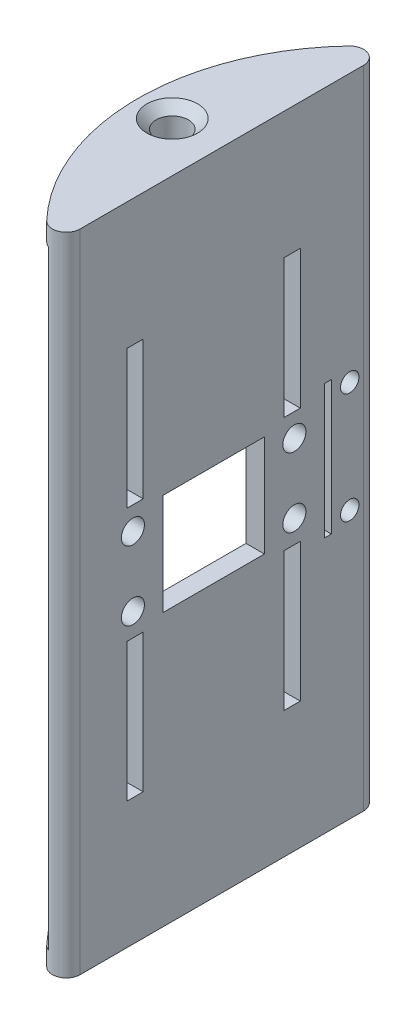
SolidWorks part; units mm, degrees
ref_plane "Front Plane" through (0, 0, 0) normal (1, 0, 0) x (0, 1, 0)
ref_plane "Top Plane" through (0, 0, 0) normal (0, 0, 1) x (0, 1, 0)
ref_plane "Right Plane" through (0, 0, 0) normal (0, 1, 0) x (-1, 0, 0)
sketch "Sketch1" plane through (0, 0, 0) normal (0, 0, 1) x (0, 1, 0)
  line L0 (-8.186, 0) -> (-8.186, -21.2483)
  line L1 (-8.186, -21.2483) -> (131.814, -21.2483)
  line L2 (131.814, -21.2483) -> (131.814, 0)
  line L3 (131.814, 0) -> (123.814, 0)
  line L4 (123.814, 0) -> (123.814, -17.2483)
  line L5 (123.814, -17.2483) -> (-0.186, -17.2483)
  line L6 (-0.186, -17.2483) -> (-0.186, 0)
  line L7 (-0.186, 0) -> (-8.186, 0)
  line L8 (-12.186, -30.6238) -> (-12.186, -16.002) construction
  line L10 (135.814, -16.002) -> (135.814, 53.9758) construction
  dimension "D1" = 4
  dimension "D2" = 8
  dimension "D3" = 4
  dimension "D4" = 4
  dimension "D5" = 140
extrude "Boss-Extrude1" add sketch "Sketch1" along normal blind 75
sketch "Sketch2" plane through (0, -8.186, 0) normal (0, -1, 0) x (1, 0, 0)
  line L0 (21.2483, 37.5) -> (0, 37.5) construction
  line L1 (21.2483, 75) -> (21.2483, 0) construction
  line L2 (0, 75) -> (0, 0) construction
  circle A0 centre (10.5, 37.5) radius 3.5
  dimension "D1" = 7
  dimension "D2" = 7
extrude "Cut-Extrude1" cut sketch "Sketch2" against normal offset from surface (7 mm away) 1 up to face at (8.6242, -0.186, 37.5)
sketch "Sketch3" plane through (0, 131.814, 0) normal (0, 1, 0) x (-1, 0, 0)
  circle A0 centre (-10.5, 37.5) radius 3.5 construction
  circle A1 centre (-10.5, 37.5) radius 3.5
extrude "Cut-Extrude2" cut sketch "Sketch3" against normal offset from surface (7 mm away) 1 up to face at (8.6242, 123.814, 37.5)
sketch "Sketch6" plane through (0, -0.186, 0) normal (0, 1, 0) x (-1, 0, 0)
  line L4 (-17.2483, 0) -> (0, 0)
  line L5 (0, 0) -> (0, 75)
  line L6 (0, 75) -> (-17.2483, 75)
  line L7 (-17.2483, 75) -> (-17.2483, 0)
  line L8 (-17.2483, 0) -> (0, 0)
  line L9 (0, 0) -> (0, 75)
  line L10 (0, 75) -> (-17.2483, 75)
  line L11 (-17.2483, 75) -> (-17.2483, 0)
  circle A1 centre (-10.5, 37.5) radius 4
  circle A3 centre (-10.5, 37.5) radius 3.5 construction
  dimension "D2" = 8
  dimension "D1" = 0
extrude "Cut-Extrude3" cut sketch "Sketch6" against normal blind 4
sketch "Sketch7" plane through (0, 123.814, 0) normal (0, -1, 0) x (1, 0, 0)
  line L4 (0, 0) -> (17.2483, 0)
  line L5 (17.2483, 0) -> (17.2483, 75)
  line L6 (17.2483, 75) -> (0, 75)
  line L7 (0, 75) -> (0, 0)
  line L8 (0, 0) -> (17.2483, 0)
  line L9 (17.2483, 0) -> (17.2483, 75)
  line L10 (17.2483, 75) -> (0, 75)
  line L11 (0, 75) -> (0, 0)
  circle A2 centre (10.5, 37.5) radius 4
  circle A3 centre (10.5, 37.5) radius 3.5 construction
  dimension "D1" = 8
  dimension "D2" = 0
extrude "Cut-Extrude4" cut sketch "Sketch7" against normal blind 4
fillet "Fillet6" radius 4 2 edges at (10.5, 127.814, 33.5) (10.5, -4.186, 41.5)
chamfer "Chamfer1" distance 2 angle 45 2 edges at (10.5, -8.186, 34) (10.5, 131.814, 41)
sketch "Sketch10" plane through (0, -8.186, 0) normal (0, -1, 0) x (1, 0, 0)
  line L6 (21.2483, 75) -> (0, 75)
  line L7 (0, 75) -> (0, 0) construction
  line L8 (0, 75) -> (21.2483, 75) construction
  line L9 (0, 75) -> (0, 0)
  line L10 (0, 0) -> (21.2483, 0)
  arc A1 (21.2483, 75) -> (21.2483, 0) centre (50.6551, 37.5) ccw
  circle A4 centre (10.5, 37.5) radius 5.5 construction
  dimension "D1" = 2
extrude "Cut-Extrude9" cut sketch "Sketch10" against normal through all
fillet "Fillet11" radius 3 2 edges at (21.2483, 61.814, 75) (21.2483, 61.814, 0)
sketch "Sketch14" plane through (21.2483, 0, 0) normal (1, 0, 0) x (0, 1, 0)
  line L2 (131.814, 5.8571) -> (131.814, 74.4281) construction
  line L3 (-8.186, 74.4281) -> (-8.186, 5.8571) construction
  line L4 (-8.186, 40.1426) -> (131.814, 40.1426) construction
  line L5 (61.814, 8.6855) -> (61.814, 71.5997) construction
  line L8 (104.314, 58.0522) -> (74.314, 58.0522)
  line L9 (19.314, 54.5522) -> (49.314, 54.5522)
  line L10 (19.314, 54.5522) -> (19.314, 58.0522)
  line L11 (19.314, 58.0522) -> (49.314, 58.0522)
  line L12 (49.314, 54.5522) -> (49.314, 58.0522)
  line L13 (19.314, 54.5522) -> (49.314, 58.0522) construction
  line L14 (19.314, 58.0522) -> (49.314, 54.5522) construction
  line L15 (74.314, 54.5522) -> (74.314, 58.0522)
  line L16 (104.314, 54.5522) -> (74.314, 54.5522)
  line L17 (104.314, 54.5522) -> (104.314, 58.0522)
  line L18 (54.314, 56.7774) -> (54.314, 21.7774) construction
  line L19 (54.314, 39.2774) -> (68.2197, 39.2774) construction
  line L20 (104.314, 24.0026) -> (104.314, 20.5026)
  line L21 (104.314, 24.0026) -> (74.314, 24.0026)
  line L22 (74.314, 24.0026) -> (74.314, 20.5026)
  line L23 (104.314, 20.5026) -> (74.314, 20.5026)
  line L24 (19.314, 20.5026) -> (49.314, 20.5026)
  line L25 (49.314, 24.0026) -> (49.314, 20.5026)
  line L26 (19.314, 24.0026) -> (49.314, 24.0026)
  line L27 (19.314, 24.0026) -> (19.314, 20.5026)
  line L28 (-8.186, 68.2226) -> (-8.186, 6.7774) construction
  line L29 (131.814, 68.2226) -> (131.814, 6.7774) construction
  line L30 (-8.186, 6.7774) -> (131.814, 6.7774) construction
  circle A0 centre (54.314, 21.7774) radius 2.5
  circle A1 centre (54.314, 56.7774) radius 2.5
  circle A2 centre (69.314, 56.7774) radius 2.5
  circle A3 centre (69.314, 21.7774) radius 2.5
  circle A4 centre (49.814, 9.7774) radius 2
  circle A5 centre (73.814, 9.7774) radius 2
  point P24 (34.314, 56.3022)
  point P45 (61.814, 6.7774)
  dimension "D3" = 2.5
  dimension "D4" = 5
  dimension "D8" = 4
  dimension "D1" = 3.5
  dimension "D2" = 30
  dimension "D5" = 15
  dimension "D6" = 35
  dimension "D7" = 15
  dimension "D9" = 24
  dimension "D10" = 3
extrude "Cut-Extrude13" cut sketch "Sketch14" against normal up to next
sketch "Sketch16" plane through (21.2483, 0, 0) normal (1, 0, 0) x (0, 1, 0)
  line L0 (54.314, 21.7774) -> (69.314, 56.7774) construction
  line L1 (54.314, 56.7774) -> (69.314, 21.7774) construction
  line L3 (50.814, 28.2774) -> (72.814, 28.2774)
  line L4 (50.814, 28.2774) -> (50.814, 50.2774)
  line L5 (50.814, 50.2774) -> (72.814, 50.2774)
  line L6 (72.814, 28.2774) -> (72.814, 50.2774)
  line L7 (50.814, 28.2774) -> (72.814, 50.2774) construction
  line L8 (50.814, 50.2774) -> (72.814, 28.2774) construction
  point P8 (61.814, 39.2774)
  dimension "D1" = 22
extrude "Cut-Extrude14" cut sketch "Sketch16" against normal up to next
sketch "Sketch17" plane through (17.2483, 0, 0) normal (-1, 0, 0) x (0, -1, 0)
  line L0 (-127.814, 43.0156) -> (-3.6818, 43.0156) construction
  line L7 (-41.814, 50) -> (-39.814, 50)
  line L8 (-41.814, 50) -> (-41.814, 42.5)
  line L9 (-41.814, 42.5) -> (-39.814, 42.5)
  line L10 (-39.814, 50) -> (-39.814, 42.5)
  line L11 (-28.814, 50) -> (-26.814, 50)
  line L12 (-28.814, 50) -> (-28.814, 42.5)
  line L13 (-28.814, 42.5) -> (-26.814, 42.5)
  line L14 (-26.814, 50) -> (-26.814, 42.5)
  line L15 (-49.314, 58.0522) -> (-49.314, 54.5522) construction
  line L16 (-26.814, 25) -> (-26.814, 43.5312)
  line L17 (-28.814, 43.5312) -> (-26.814, 43.5312)
  line L18 (-28.814, 25) -> (-28.814, 43.5312)
  line L19 (-28.814, 25) -> (-26.814, 25)
  line L20 (-39.814, 13.9688) -> (-39.814, 43.5312)
  line L21 (-41.814, 43.5312) -> (-39.814, 43.5312)
  line L22 (-41.814, 13.9688) -> (-41.814, 43.5312)
  line L23 (-41.814, 13.9688) -> (-39.814, 13.9688)
  line L24 (-127.814, 40.5312) -> (-127.814, 45.5) construction
  line L25 (-41.814, 46.25) -> (-39.814, 46.25) construction
  line L26 (-39.814, 28.75) -> (-41.814, 28.75) construction
  dimension "D1" = 11
  dimension "D2" = 2
  dimension "D3" = 7.5
  dimension "D4" = 17.5
  dimension "D5" = 7.5
sketch "Sketch18" plane through (0, -0.186, 0) normal (0, 1, 0) x (-1, 0, 0)
  circle A0 centre (-10.5, 37.5) radius 2
  dimension "D1" = 4
extrude "Cut-Extrude15" cut sketch "Sketch18" against normal through all both and the other way through all
sketch "Sketch19" plane through (21.2483, 0, 0) normal (1, 0, 0) x (0, 1, 0)
  line L0 (73.814, 15.2774) -> (49.814, 15.2774) construction
  line L1 (76.314, 15.2774) -> (47.314, 15.2774)
  line L2 (47.314, 13.7774) -> (76.314, 13.7774) construction
  line L3 (47.314, 13.7774) -> (76.314, 13.7774)
  line L4 (76.314, 13.7774) -> (76.314, 15.2774)
  line L5 (47.314, 13.7774) -> (47.314, 15.2774)
extrude "Cut-Extrude16" cut sketch "Sketch19" against normal up to next
ref_plane "Plane1" through (0, 41.814, 0) normal (0, -1, 0) x (1, 0, 0)
